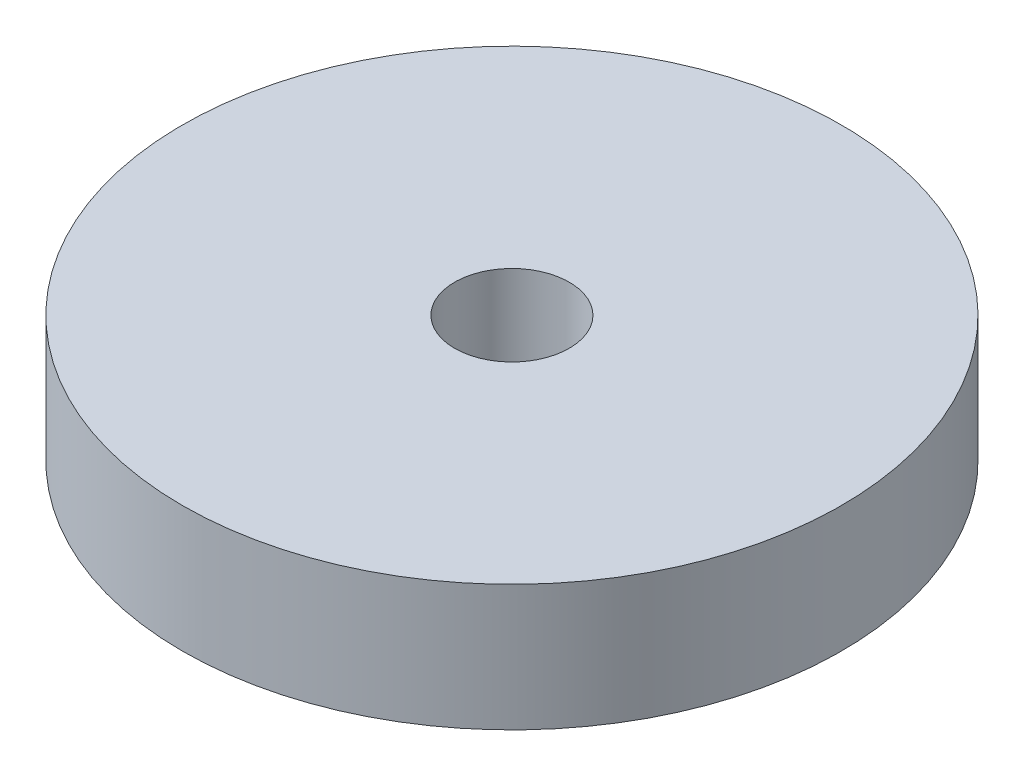
SolidWorks part; units mm, degrees
ref_plane "Front Plane" through (0, 0, 0) normal (0, 0, 1) x (1, 0, 0)
ref_plane "Top Plane" through (0, 0, 0) normal (0, 1, 0) x (1, 0, 0)
ref_plane "Right Plane" through (0, 0, 0) normal (1, 0, 0) x (0, 0, -1)
sketch "Sketch1" plane through (0, 0, 0) normal (0, 1, 0) x (1, 0, 0)
  circle A0 centre (0, 0) radius 57.5
  dimension "FLANGE_OD" = 115
extrude "Boss-Extrude1" add sketch "Sketch1" along normal blind 22
sketch "Sketch2" plane through (0, 0, 0) normal (0, 1, 0) x (1, 0, 0)
  circle A0 centre (0, 0) radius 10
  dimension "BORE_D" = 20
extrude "Cut-Extrude1" cut sketch "Sketch2" along normal through all
sketch "Sketch3" plane through (0, 22, 0) normal (0, 1, 0) x (1, 0, 0)
  circle A0 centre (0, 0) radius 6.348 construction
  circle A1 centre (-6.348, 0) radius 1.59
  dimension "BOLT_D" = 3.18
  dimension "BOLT_PCD" = 12.696
extrude "Cut-Extrude2" cut sketch "Sketch3" against normal blind 19.5899 rebuild error yes
pattern_circular "CirPattern1" count 8 over 360 rebuild error yes
